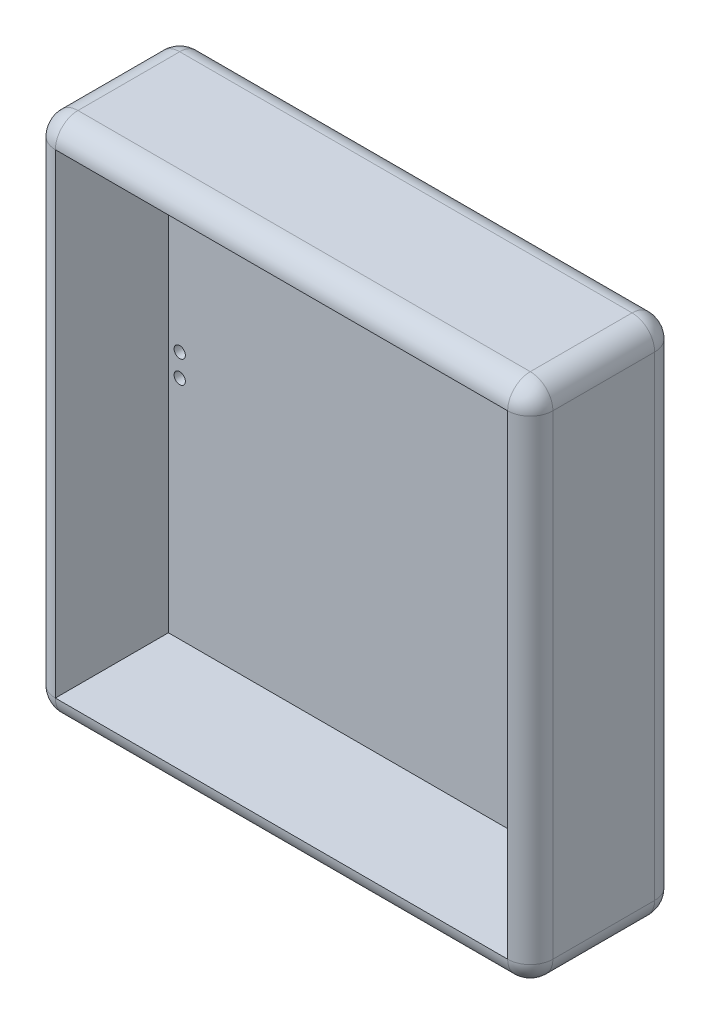
SolidWorks part; units mm, degrees
ref_plane "前视基准面" through (0, 0, 0) normal (0, 0, 1) x (1, 0, 0)
ref_plane "上视基准面" through (0, 0, 0) normal (0, 1, 0) x (1, 0, 0)
ref_plane "右视基准面" through (0, 0, 0) normal (1, 0, 0) x (0, 0, -1)
sketch "草图1" plane through (0, 0, 0) normal (0, 0, 1) x (1, 0, 0)
  line L0 (0, 0) -> (0, 42)
  line L1 (0, 0) -> (-40, 0)
  line L2 (0, 0) -> (0, -2)
  line L3 (0, -2) -> (2, -2)
  line L4 (2, -2) -> (2, 44)
  line L5 (0, 42) -> (-40, 42)
  line L6 (-40, 42) -> (-40, 0)
  line L7 (0, -2) -> (-42, -2)
  line L8 (-42, -2) -> (-42, 44)
  line L9 (-42, 44) -> (2, 44)
extrude "凸台-拉伸1" add sketch "草图1" along normal blind 10 contours L9 L8 L7 L1 L6 L5 L0 L3 L4 region at (-21, -1.3634, 0)
sketch "草图2" plane through (0, 0, 0) normal (0, 0, 1) x (1, 0, 0)
  line L0 (2, -2) -> (2, 44) construction
  line L1 (-42, 44) -> (2, 44)
  line L2 (-42, 44) -> (-42, -2)
  line L3 (-42, -2) -> (2, -2)
  line L4 (2, 44) -> (2, -2)
extrude "凸台-拉伸2" add sketch "草图2" against normal blind 3
fillet "圆角1" radius 2 1 edges at (-20, 44, -3)
fillet "圆角2" radius 2 3 edges at (2, 44, 4.5) (2, 43.4142, -2.4142) (2, 20, -3)
fillet "圆角3" radius 2 5 edges at (-42, -2, 3.5) (-20, -2, 10) (2, -2, 4.5) (1.4142, -2, -2.4142) (-21, -2, -3)
fillet "圆角4" radius 2 4 edges at (1.4142, -1.4142, 9.4142) (-21, 44, 10) (1.4142, 43.4142, 10) (2, 21, 10)
fillet "圆角5" radius 2 7 edges at (-41.4142, -1.4142, 9.4142) (-42, 21, 10) (-42, 43.4142, 9.4142) (-42, 44, 3.5) (-42, 43.4142, -2.4142) (-41.4142, -1.4142, -2.4142) (-42, 21, -3)
sketch "草图4" plane through (0, 0, 0) normal (0, 0, 1) x (1, 0, 0)
  circle A0 centre (-39, 22) radius 0.5
  circle A1 centre (-39, 20) radius 0.5
extrude "切除-拉伸1" cut sketch "草图4" against normal blind 3
